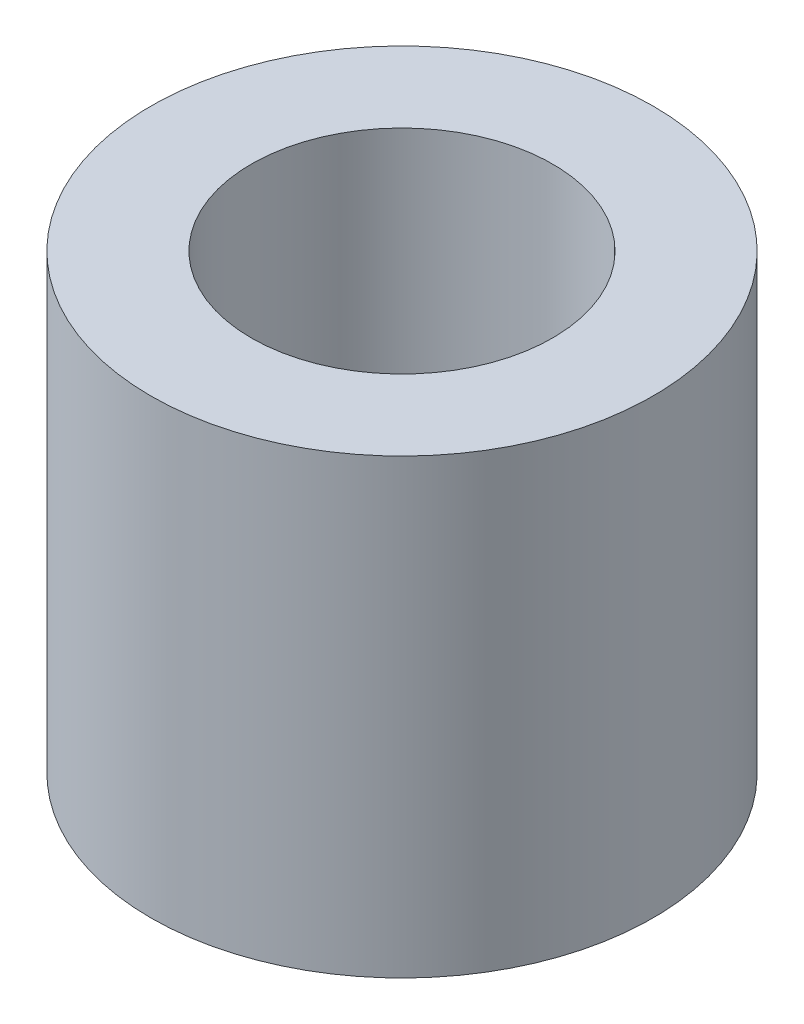
SolidWorks part; units mm, degrees
ref_plane "Front Plane" through (0, 0, 0) normal (0, 0, 1) x (1, 0, 0)
ref_plane "Top Plane" through (0, 0, 0) normal (0, 1, 0) x (1, 0, 0)
ref_plane "Right Plane" through (0, 0, 0) normal (1, 0, 0) x (0, 0, -1)
sketch "Sketch1" plane through (0, 0, 0) normal (0, 1, 0) x (1, 0, 0)
  circle A0 centre (0, 0) radius 5
  circle A1 centre (0, 0) radius 3
  dimension "D1" = 10
  dimension "D2" = 6
extrude "Boss-Extrude1" add sketch "Sketch1" along normal blind 4.5 and the other way blind 4.5
